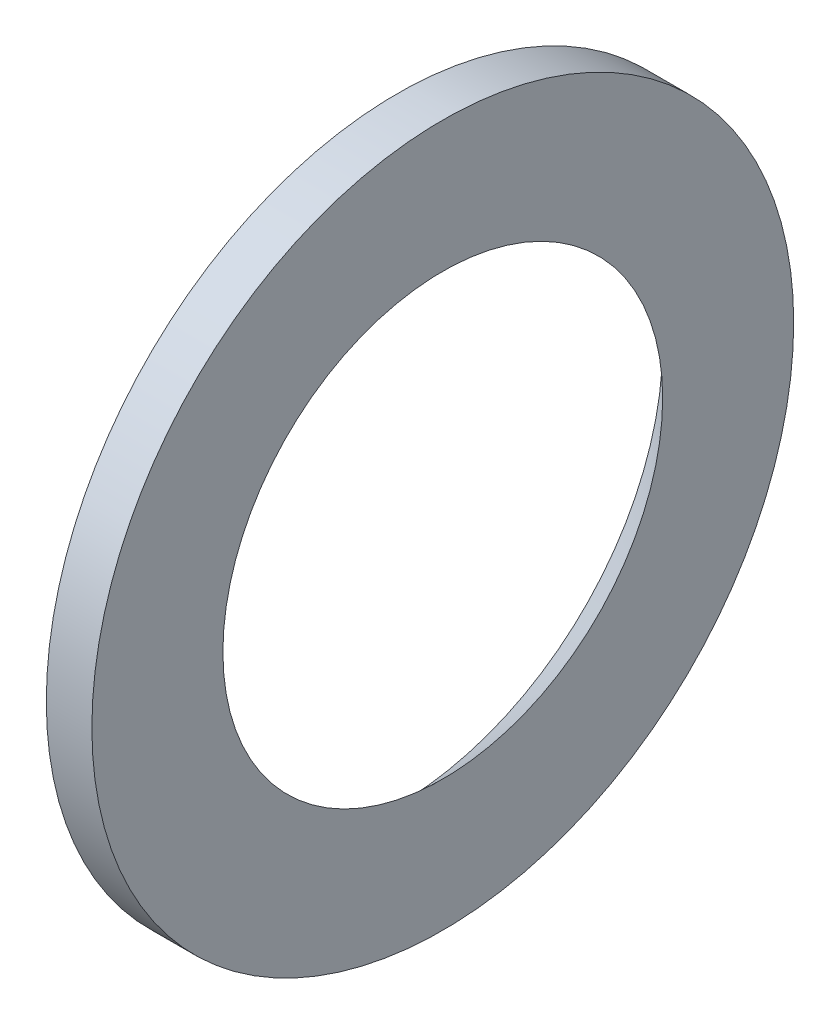
SolidWorks part; units mm, degrees
material "5052-H32"
ref_plane "Přední rovina" through (0, 0, 0) normal (0, 0, 1) x (1, 0, 0)
ref_plane "Horní rovina" through (0, 0, 0) normal (0, 1, 0) x (1, 0, 0)
ref_plane "Pravá rovina" through (0, 0, 0) normal (1, 0, 0) x (0, 0, -1)
sketch "Skica2" plane through (0, 0, 0) normal (0, 0, 1) x (1, 0, 0)
  line L0 (-324.05, -15.4) -> (-322.05, -15.4) construction
  line L1 (-324.05, -11.65) -> (-324.05, -15.4) construction
  line L2 (-322.05, -15.4) -> (-322.05, -9.65) construction
  line L3 (-322.05, -9.65) -> (-324.05, -11.65) construction
  line L4 (-324.05, -15.4) -> (-322.05, -15.4)
  line L5 (-324.05, -11.65) -> (-324.05, -15.4)
  line L6 (-322.05, -15.4) -> (-322.05, -9.65)
  line L7 (-322.05, -9.65) -> (-324.05, -11.65)
  line L8 (-67.4823, 0) -> (-363.0393, 0) construction
  line L9 (-67.4823, 0) -> (-353.9165, 0) construction
  point P6 (-353.9165, 0)
revolve "Rotovat2" add sketch "Skica2" angle 360 about L9
